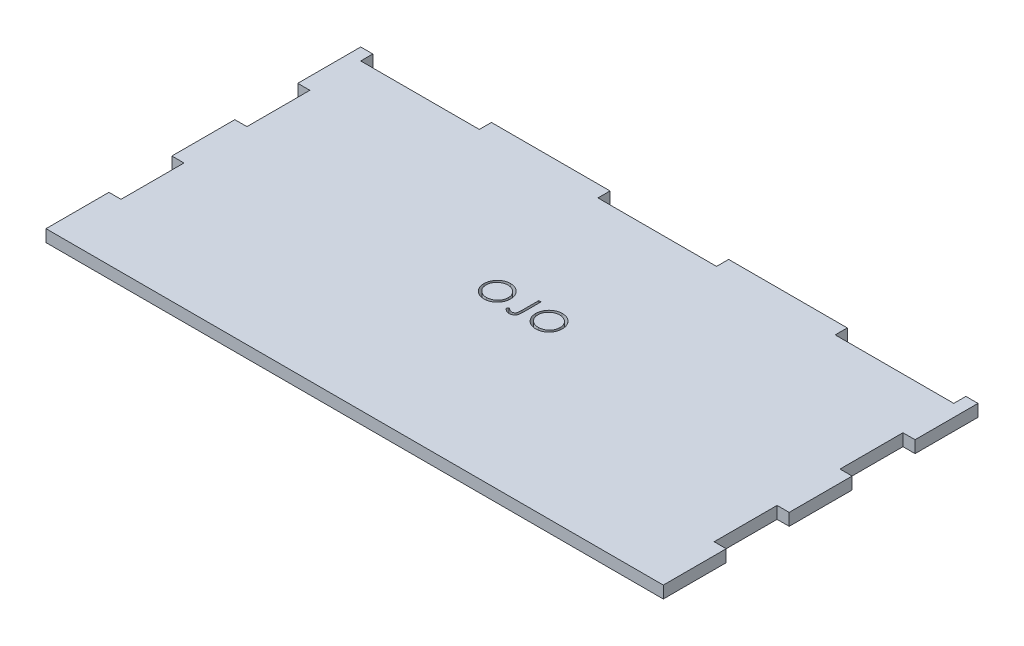
SolidWorks part; units mm, degrees
ref_plane "Front Plane" through (0, 0, 0) normal (0, 0, 1) x (1, 0, 0)
ref_plane "Top Plane" through (0, 0, 0) normal (0, 1, 0) x (1, 0, 0)
ref_plane "Right Plane" through (0, 0, 0) normal (1, 0, 0) x (0, 0, -1)
sketch "Sketch1" plane through (0, 0, 0) normal (0, 1, 0) x (1, 0, 0)
  line L6 (-73.5, 33) -> (-44.1, 33)
  line L12 (-73.5, 20.4) -> (-73.5, 4.8)
  line L14 (-76.5, 36) -> (-73.5, 36)
  line L16 (-76.5, 36) -> (-76.5, 20.4)
  line L20 (-76.5, 4.8) -> (-76.5, -10.8)
  line L23 (-76.5, -26.4) -> (-76.5, -42)
  line L24 (-76.5, -26.4) -> (-73.5, -26.4)
  line L25 (-76.5, -10.8) -> (-73.5, -10.8)
  line L26 (-76.5, 4.8) -> (-73.5, 4.8)
  line L27 (-76.5, 20.4) -> (-73.5, 20.4)
  line L29 (-73.5, 33) -> (-73.5, 36)
  line L30 (-73.5, -10.8) -> (-73.5, -26.4)
  line L31 (14.7, 36) -> (44.1, 36)
  line L32 (76.5, -26.4) -> (76.5, -42)
  line L33 (76.5, -26.4) -> (73.5, -26.4)
  line L34 (73.5, -10.8) -> (73.5, -26.4)
  line L35 (76.5, -10.8) -> (73.5, -10.8)
  line L36 (76.5, 4.8) -> (76.5, -10.8)
  line L37 (76.5, 4.8) -> (73.5, 4.8)
  line L38 (73.5, 20.4) -> (73.5, 4.8)
  line L39 (76.5, 20.4) -> (73.5, 20.4)
  line L40 (76.5, 36) -> (76.5, 20.4)
  line L41 (73.5, 33) -> (73.5, 36)
  line L43 (-14.7, 33) -> (14.7, 33)
  line L44 (73.5, 36) -> (76.5, 36)
  line L45 (44.1, 33) -> (73.5, 33)
  line L46 (-44.1, 33) -> (-44.1, 36)
  line L47 (-14.7, 33) -> (-14.7, 36)
  line L48 (14.7, 33) -> (14.7, 36)
  line L49 (44.1, 33) -> (44.1, 36)
  line L50 (-44.1, 36) -> (-14.7, 36)
  line L62 (-76.5, -42) -> (76.5, -42)
  point P0 (0, 0)
  point P4 (0, 0)
extrude "Boss-Extrude1" add sketch "Sketch1" along normal blind 3
sketch "Sketch2" plane through (0, 3, 0) normal (0, 1, 0) x (1, 0, 0)
  text T0 "OJO" font "Century Gothic" height in points 24
  point P1 (0, 0)
extrude "Cut-Extrude1" cut sketch "Sketch2" against normal through all
